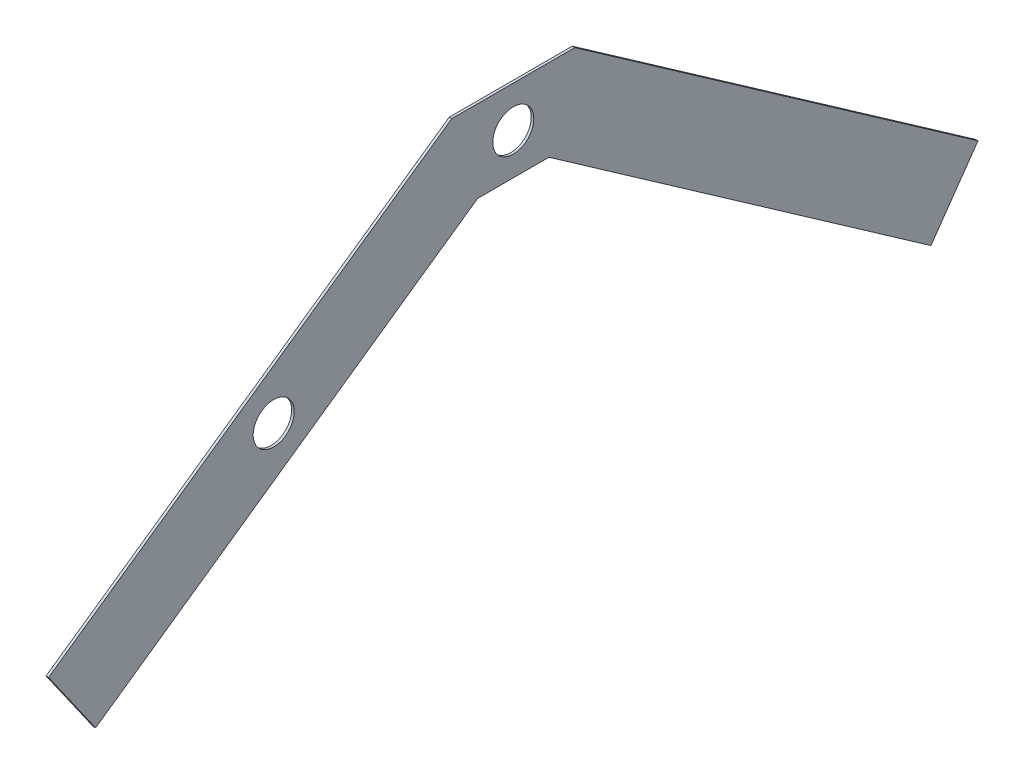
SolidWorks part; units mm, degrees
material "6063-O"
ref_plane "Front" through (0, 0, 0) normal (0, 0, 1) x (1, 0, 0)
ref_plane "Top" through (0, 0, 0) normal (0, 1, 0) x (1, 0, 0)
ref_plane "Right" through (0, 0, 0) normal (1, 0, 0) x (0, 0, -1)
sketch "Sketch2" plane through (0, 0, 0) normal (1, 0, 0) x (0, 0, -1)
  line L0 (0, 394.2537) -> (0, -55479.9958) construction
  line L1 (76.2, 101.6) -> (-76.2, 101.6)
  line L2 (-76.2, 101.6) -> (-575.5551, -248.0522)
  line L3 (-575.5551, -248.0522) -> (-517.2797, -331.278)
  line L4 (-517.2797, -331.278) -> (-44.1656, 0)
  line L5 (-44.1656, 0) -> (44.1656, 0)
  line L6 (517.2797, -331.278) -> (44.1656, 0)
  line L7 (575.5551, -248.0522) -> (517.2797, -331.278)
  line L8 (76.2, 101.6) -> (575.5551, -248.0522)
  point P2 (0, 0)
  point P13 (0, 0)
  point P14 (0, 101.6)
  dimension "D1" = 101.6
  dimension "D2" = 101.6
  dimension "D3" = 76.2
  dimension "D4" = 609.6
  dimension "D5" = 145
extrude "Boss-Extrude1" add sketch "Sketch2" along normal blind 3.175
sketch "Sketch3" plane through (3.175, 0, 0) normal (1, 0, 0) x (0, 0, -1)
  line L0 (-583.7305, -315.792) -> (38592.1147, 27115.4301) construction
  line L1 (-575.5551, -248.0522) -> (-517.2797, -331.278) construction
  line L2 (-76.2, 101.6) -> (-575.5551, -248.0522) construction
  line L3 (0, 101.6) -> (0, 0) construction
  line L4 (76.2, 101.6) -> (-76.2, 101.6) construction
  line L5 (-546.4174, -289.6651) -> (546.4174, -289.6651) construction
  line L6 (517.2797, -331.278) -> (575.5551, -248.0522) construction
  line L7 (-296.7399, -114.839) -> (0, -289.6651) construction
  circle A0 centre (0, 50.8) radius 25.4
  circle A1 centre (-296.7399, -114.839) radius 25.4
  point P8 (-546.4174, -289.6651)
  point P11 (0, -289.6651)
  dimension "D1" = 50.8
  dimension "D2" = 304.8
extrude "Cut-Extrude1" cut sketch "Sketch3" against normal through all
